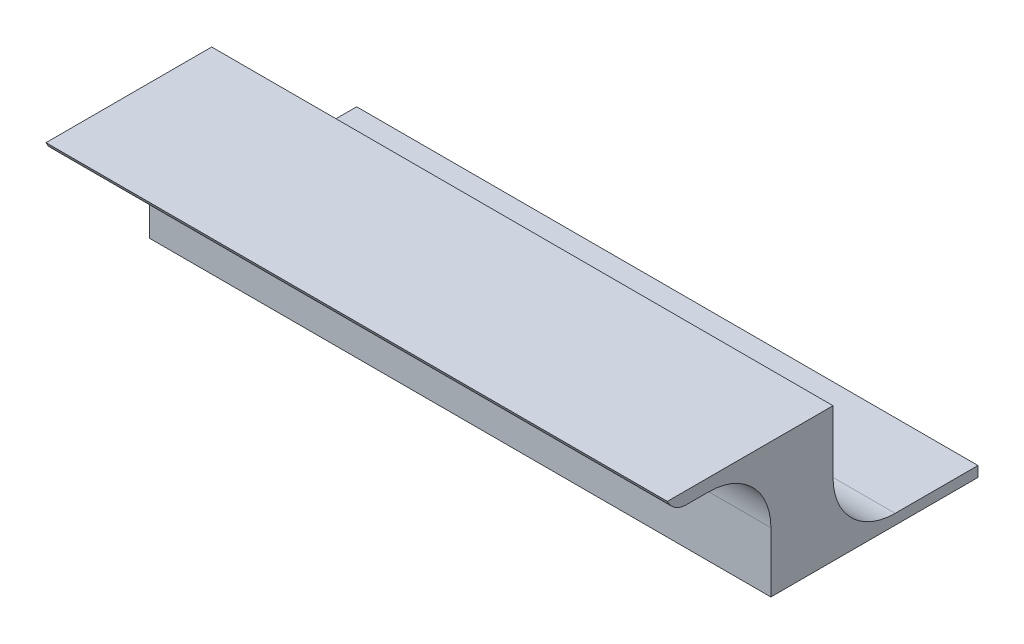
SolidWorks part; units mm, degrees
ref_plane "Front Plane" through (0, 0, 0) normal (0, 0, 1) x (1, 0, 0)
ref_plane "Top Plane" through (0, 0, 0) normal (0, 1, 0) x (1, 0, 0)
ref_plane "Right Plane" through (0, 0, 0) normal (1, 0, 0) x (0, 0, -1)
sketch "Sketch1" plane through (0, 0, 0) normal (0, 1, 0) x (1, 0, 0)
  line L1 (15, 5) -> (-15, 5)
  line L2 (15, 5) -> (15, -5)
  line L3 (15, -5) -> (-15, -5)
  line L4 (-15, 5) -> (-15, -5)
  line L5 (15, 5) -> (-15, -5) construction
  line L6 (15, -5) -> (-15, 5) construction
  point P0 (0, 0)
  dimension "D1" = 30
  dimension "D2" = 10
extrude "Boss-Extrude1" add sketch "Sketch1" along normal blind 0.5
sketch "Sketch2" plane through (0, 0.5, 0) normal (0, 1, 0) x (1, 0, 0)
  line L0 (15, -5) -> (15, 5) construction
  line L1 (-15, -5) -> (15, -5)
  line L2 (-15, -5) -> (-15, -2)
  line L3 (-15, -2) -> (15, -2)
  line L4 (15, -5) -> (15, -2)
  dimension "D1" = 3
extrude "Boss-Extrude2" add sketch "Sketch2" along normal blind 6
sketch "Sketch3" plane through (0, 0, 5) normal (0, 0, 1) x (1, 0, 0)
  line L1 (-15, 6.5) -> (15, 6.5)
  line L2 (-15, 6.5) -> (-15, 5.9)
  line L3 (-15, 5.9) -> (15, 5.9)
  line L4 (15, 6.5) -> (15, 5.9)
  point P5 (15, 6.5)
  dimension "D1" = 0.6
extrude "Boss-Extrude3" add sketch "Sketch3" along normal blind 5
fillet "Fillet1" radius 3 2 edges at (0, 0.5, 2) (0, 5.9, 5)
fillet "Fillet2" radius 1 1 edges at (0, 5.9, 10)
